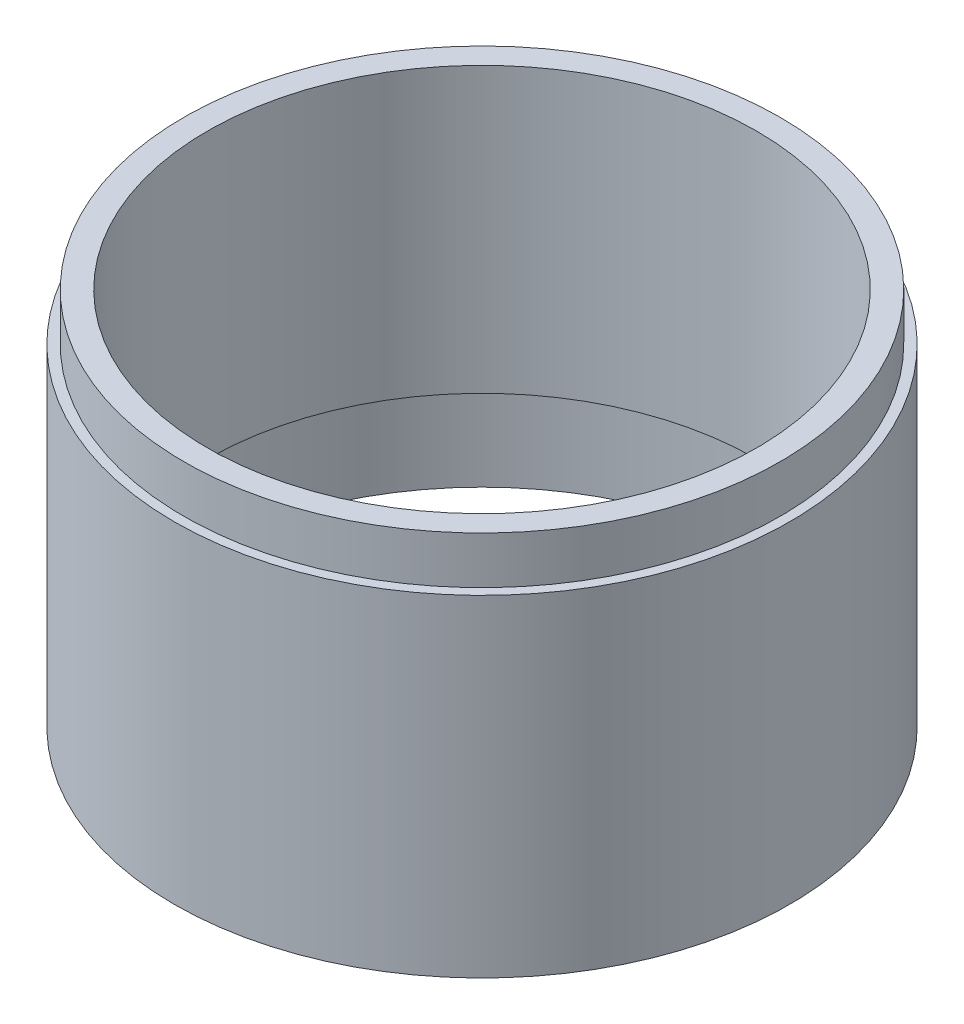
SolidWorks part; units mm, degrees
material "HYPALON"
ref_plane "Front Plane" through (0, 0, 0) normal (0, 0, 1) x (1, 0, 0)
ref_plane "Top Plane" through (0, 0, 0) normal (0, 1, 0) x (1, 0, 0)
ref_plane "Right Plane" through (0, 0, 0) normal (1, 0, 0) x (0, 0, -1)
sketch "Szkic1" plane through (0, 0, 0) normal (0, 0, 1) x (1, 0, 0)
  line L0 (0, 0) -> (-65, 0)
  line L1 (-65, 0) -> (-65, 20)
  line L2 (-62, 20) -> (-58, 20)
  line L3 (-58, 20) -> (-58, 80)
  line L4 (-62, 20) -> (-62, 0)
  line L5 (-58, 80) -> (-63, 80)
  line L7 (-65, 20) -> (-65, 70)
  line L8 (-65, 70) -> (-63, 70)
  line L9 (-63, 70) -> (-63, 80)
  line L13 (0, 0) -> (0, 22.4148)
  dimension "D1" = 65
  dimension "D2" = 20
  dimension "D3" = 7
  dimension "D4" = 80
  dimension "D5" = 3
  dimension "D7" = 2
  dimension "D8" = 10
revolve "Obrót1" add sketch "Szkic1" angle 360 about L13 region at (-61.6522, 43.6957, 0)
